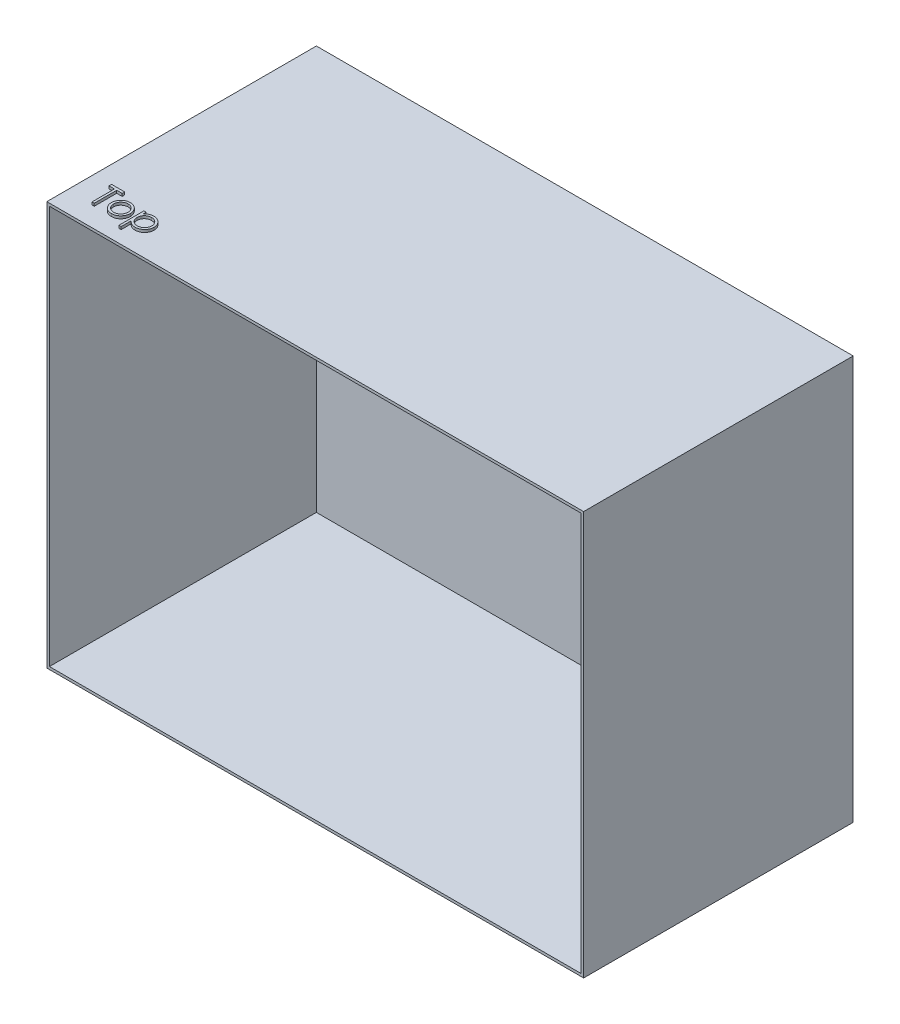
SolidWorks part; units mm, degrees
ref_plane "Front Plane" through (0, 0, 0) normal (0, 0, 1) x (1, 0, 0)
ref_plane "Top Plane" through (0, 0, 0) normal (0, 1, 0) x (1, 0, 0)
ref_plane "Right Plane" through (0, 0, 0) normal (1, 0, 0) x (0, 0, -1)
sketch "Sketch1" plane through (0, 0, 0) normal (0, 0, 1) x (1, 0, 0)
  line L0 (-204.32, 153.74) -> (204.32, 153.74)
  line L1 (-202.32, 151.74) -> (202.32, 151.74)
  line L2 (-202.32, 151.74) -> (-202.32, -151.74)
  line L3 (-202.32, -151.74) -> (202.32, -151.74)
  line L4 (202.32, 151.74) -> (202.32, -151.74)
  line L5 (204.32, 153.74) -> (204.32, -153.74)
  line L6 (-204.32, -153.74) -> (204.32, -153.74)
  line L7 (-204.32, 153.74) -> (-204.32, -153.74)
  point P9 (0, 0)
  dimension "D1" = 404.64
  dimension "D2" = 303.48
  dimension "D3" = 202.32
  dimension "D4" = 151.74
  dimension "D5" = 2
extrude "Boss-Extrude1" add sketch "Sketch1" against normal blind 2 contours L0 L5 L6 L7
extrude "Boss-Extrude4" add sketch "Sketch1<6>" along normal blind 203.2
sketch "Sketch1<6>" plane through (0, 0, 0) normal (0, 0, 1) x (1, 0, 0) same geometry as "Sketch1"
sketch "Sketch4" plane through (0, 153.74, 0) normal (0, 1, 0) x (1, 0, 0)
  line L0 (-204.32, 2) -> (-204.32, -203.2) construction
  line L1 (204.32, -203.2) -> (-204.32, -203.2) construction
  text T0 "Top" font "Century Gothic" height in points 72
  point P1 (-42.582, -120.6858)
  point P2 (0, 0)
  point P3 (-204.32, -203.2)
  point P4 (-204.32, -203.2)
  point P5 (-187.5977, -182.0406)
  dimension "D1" = 15
  dimension "D2" = 15
extrude "Boss-Extrude5" add sketch "Sketch4" along normal blind 2
equation "\"D2@Sketch1\"=\"D1@Sketch1\"*3/4"
equation "\"D4@Sketch1\"=\"D2@Sketch1\"/2"
equation "\"D3@Sketch1\"=\"D1@Sketch1\"/2"
